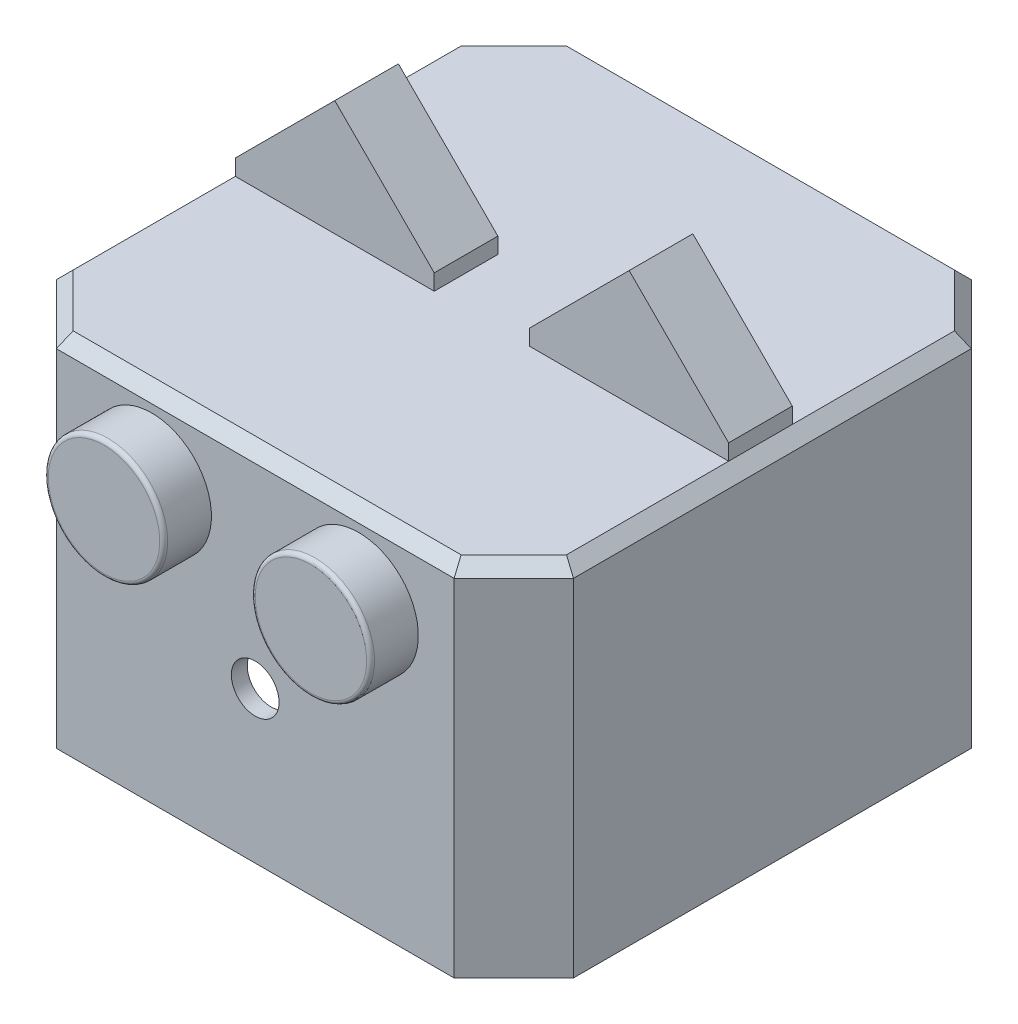
SolidWorks part; units mm, degrees
ref_plane "Alzado" through (0, 0, 0) normal (0, 0, 1) x (1, 0, 0)
ref_plane "Planta" through (0, 0, 0) normal (0, 1, 0) x (1, 0, 0)
ref_plane "Vista lateral" through (0, 0, 0) normal (1, 0, 0) x (0, 0, -1)
sketch "Croquis1" plane through (0, 0, 0) normal (0, 1, 0) x (1, 0, 0)
  line L1 (-25, -32.5) -> (25, -32.5)
  line L3 (-25, 32.5) -> (25, 32.5)
  line L5 (-25, -32.5) -> (25, 32.5) construction
  line L6 (-25, 32.5) -> (25, -32.5) construction
  line L10 (32.5, 25) -> (32.5, -25)
  line L11 (25, -32.5) -> (32.5, -25)
  line L12 (32.5, 25) -> (25, 32.5)
  line L13 (-32.5, 25) -> (-32.5, -25)
  line L14 (-32.5, -25) -> (-25, -32.5)
  line L15 (-32.5, 25) -> (-25, 32.5)
  point P0 (0, 0)
  point P10 (0, 32.5)
  dimension "D1" = 65
  dimension "D2" = 65
  dimension "D3" = 50
  dimension "D4" = 50
  dimension "D5" = 25
  dimension "D6" = 25
extrude "Saliente-Extruir1" add sketch "Croquis1" along normal blind 45
shell "Vaciado2" thickness 2 removed face at (0, 0, 0)
chamfer "Chaflán3" distance 1.5 angle 45 8 edges at (0, 45, -32.5) (32.5, 45, 0) (0, 45, 32.5) (-32.5, 45, 0) (-28.75, 45, 28.75) (28.75, 45, 28.75) (28.75, 45, -28.75) (-28.75, 45, -28.75)
sketch "Croquis2" plane through (0, 0, 32.5) normal (0, 0, 1) x (1, 0, 0)
  line L0 (0, 0) -> (0, 6.916) construction
  circle A0 centre (13, 35) radius 7.5
  circle A1 centre (-13, 35) radius 7.5
  dimension "D1" = 15
  dimension "D2" = 13
  dimension "D3" = 35
extrude "Saliente-Extruir2" add sketch "Croquis2" along normal blind 6
sketch "Croquis4" plane through (0, 0, 30.5) normal (0, 0, -1) x (-1, 0, 0)
  line L0 (0, 0) -> (0, 4.7403) construction
  line L1 (0, 0) -> (0, 6.916) construction
  circle A0 centre (-13, 35) radius 5
  circle A1 centre (13, 35) radius 5
  dimension "D1" = 10
extrude "Cortar-Extruir2" cut sketch "Croquis4" against normal blind 5
fillet "Redondeo1" radius 0.5 2 edges at (-20.5, 35, 38.5) (20.5, 35, 38.5)
sketch "Croquis5" plane through (0, 0, 32.5) normal (0, 0, 1) x (1, 0, 0)
  circle A0 centre (0, 19) radius 3
  dimension "D2" = 6
  dimension "D1" = 19
extrude "Cortar-Extruir3" cut sketch "Croquis5" against normal blind 10
sketch "Croquis6" plane through (0, 0, -32.5) normal (0, 0, -1) x (-1, 0, 0)
  line L1 (-21, 3) -> (-15, 3)
  line L2 (-21, 3) -> (-21, 9)
  line L3 (-21, 9) -> (-15, 9)
  line L4 (-15, 3) -> (-15, 9)
  line L5 (-21, 3) -> (-15, 9) construction
  line L6 (-21, 9) -> (-15, 3) construction
  point P0 (-18, 6)
  dimension "D1" = 18
  dimension "D2" = 6
  dimension "D3" = 6
  dimension "D4" = 3
extrude "Cortar-Extruir4" cut sketch "Croquis6" against normal blind 10
sketch "Croquis13" plane through (0, 0, 35.5) normal (0, 0, -1) x (-1, 0, 0)
  circle A0 centre (-13, 35) radius 2.6
  circle A1 centre (13, 35) radius 2.6
  circle A2 centre (13, 35) radius 5
  circle A3 centre (-13, 35) radius 5
  dimension "D1" = 5.2
  dimension "D2" = 5.2
extrude "Saliente-Extruir8" add sketch "Croquis13" along normal blind 5
sketch "Croquis7" plane through (0, 0, 30.5) normal (0, 0, -1) x (-1, 0, 0)
  line L0 (24.1716, 0) -> (-24.1716, 0) construction
  line L1 (-13.58, 8.5) -> (-9.58, 8.5)
  line L2 (-13.58, 8.5) -> (-13.58, 12.5)
  line L3 (-13.58, 12.5) -> (-9.58, 12.5)
  line L4 (-9.58, 8.5) -> (-9.58, 12.5)
  line L5 (-13.58, 8.5) -> (-9.58, 12.5) construction
  line L6 (-13.58, 12.5) -> (-9.58, 8.5) construction
  line L8 (-13.58, 26) -> (-9.58, 26)
  line L9 (-13.58, 26) -> (-13.58, 30)
  line L10 (-13.58, 30) -> (-9.58, 30)
  line L11 (-9.58, 26) -> (-9.58, 30)
  line L12 (-13.58, 26) -> (-9.58, 30) construction
  line L13 (-13.58, 30) -> (-9.58, 26) construction
  line L14 (13.43, 12.5) -> (9.43, 8.5) construction
  line L15 (13.43, 8.5) -> (9.43, 12.5) construction
  line L16 (9.43, 8.5) -> (9.43, 12.5)
  line L17 (13.43, 12.5) -> (9.43, 12.5)
  line L18 (13.43, 8.5) -> (13.43, 12.5)
  line L19 (13.43, 8.5) -> (9.43, 8.5)
  line L20 (13.43, 30) -> (9.43, 26) construction
  line L21 (13.43, 26) -> (9.43, 30) construction
  line L22 (9.43, 26) -> (9.43, 30)
  line L23 (13.43, 30) -> (9.43, 30)
  line L24 (13.43, 26) -> (13.43, 30)
  line L25 (13.43, 26) -> (9.43, 26)
  point P0 (-11.58, 10.5)
  point P8 (-11.58, 28)
  point P13 (0, 0)
  point P15 (11.43, 10.5)
  point P16 (11.43, 28)
  point P20 (11.43, 10.5)
  point P25 (11.43, 28)
  point P26 (-11.58, 28)
  point P27 (11.43, 28)
  point P28 (11.43, 10.5)
  point P29 (-11.58, 10.5)
  dimension "D1" = 10.5
  dimension "D2" = 4
  dimension "D3" = 4
  dimension "D4" = 11.58
  dimension "D5" = 4
  dimension "D6" = 4
  dimension "D7" = 28
  dimension "D8" = 23.01
  dimension "D9" = 23.01
  dimension "D10" = 4
  dimension "D11" = 4
  dimension "D12" = 4
  dimension "D13" = 4
  dimension "D14" = 10.5
  dimension "D15" = 28
extrude "Saliente-Extruir3" add sketch "Croquis7" along normal blind 1
sketch "Croquis8" plane through (0, 0, 29.5) normal (0, 0, -1) x (-1, 0, 0)
  line L0 (0, 0) -> (0, 4.8013) construction
  line L1 (24.1716, 0) -> (-24.1716, 0) construction
  circle A0 centre (-11.505, 10.4893) radius 2
  circle A1 centre (-11.505, 27.9763) radius 2
  circle A2 centre (11.505, 10.4893) radius 2
  circle A3 centre (11.505, 27.9763) radius 2
  dimension "D1" = 4
  dimension "D2" = 4
  dimension "D3" = 23.01
  dimension "D4" = 23.01
extrude "Saliente-Extruir4" add sketch "Croquis8" along normal blind 1
sketch "Croquis9" plane through (0, 0, 28.5) normal (0, 0, -1) x (-1, 0, 0)
  circle A0 centre (-11.505, 27.9763) radius 1.6
  circle A1 centre (-11.505, 10.4893) radius 1.6
  circle A2 centre (11.505, 10.4893) radius 1.6
  circle A3 centre (11.505, 27.9763) radius 1.6
  dimension "D1" = 3.2
  dimension "D2" = 3.2
  dimension "D3" = 3.2
  dimension "D4" = 3.2
extrude "Cortar-Extruir5" cut sketch "Croquis9" against normal blind 2
sketch "Croquis10" plane through (0, 45, 0) normal (0, 1, 0) x (1, 0, 0)
  line L0 (-31, 24.3787) -> (-31, -24.3787) construction
  line L1 (-31, -4) -> (-6, -4)
  line L2 (-31, -4) -> (-31, 4)
  line L3 (-31, 4) -> (-6, 4)
  line L4 (-6, -4) -> (-6, 4)
  line L5 (-31, -4) -> (-6, 4) construction
  line L6 (-31, 4) -> (-6, -4) construction
  line L7 (0, 0) -> (0, 7.307) construction
  line L8 (31, 4) -> (6, -4) construction
  line L9 (31, -4) -> (6, 4) construction
  line L10 (6, -4) -> (6, 4)
  line L11 (31, 4) -> (6, 4)
  line L12 (31, -4) -> (31, 4)
  line L13 (31, -4) -> (6, -4)
  point P0 (-18.5, 0)
  point P14 (18.5, 0)
  dimension "D1" = 25
  dimension "D2" = 8
extrude "Saliente-Extruir5" add sketch "Croquis10" along normal blind 2
sketch "Croquis11" plane through (0, 0, 4) normal (0, 0, 1) x (1, 0, 0)
  line L0 (-31, 47) -> (-6, 47)
  line L1 (-6, 47) -> (-18.5, 59.5)
  line L2 (-31, 47) -> (-18.5, 59.5)
  line L3 (0, 45) -> (0, 52) construction
  line L4 (-24.3787, 45) -> (24.3787, 45) construction
  line L5 (31, 47) -> (18.5, 59.5)
  line L6 (6, 47) -> (18.5, 59.5)
  line L7 (31, 47) -> (6, 47)
extrude "Saliente-Extruir6" add sketch "Croquis11" against normal blind 8
sketch "Croquis12" plane through (0, 43, 0) normal (0, -1, 0) x (1, 0, 0)
  line L0 (0, 0) -> (-5.199, 0) construction
  line L1 (-21.9, -8.93) -> (21.9, -8.93) construction
  line L2 (-21.9, -8.93) -> (-21.9, 8.93) construction
  line L3 (-21.9, 8.93) -> (21.9, 8.93) construction
  line L4 (21.9, -8.93) -> (21.9, 8.93) construction
  line L5 (-21.9, -8.93) -> (21.9, 8.93) construction
  line L6 (-21.9, 8.93) -> (21.9, -8.93) construction
  line L7 (0, 0) -> (0, 4.1573) construction
  circle A0 centre (-20.65, 7.68) radius 0.8
  circle A1 centre (-20.65, 7.68) radius 1.15
  circle A2 centre (-20.65, -7.68) radius 1.15
  circle A3 centre (-20.65, -7.68) radius 0.8
  circle A4 centre (20.65, 7.68) radius 1.15
  circle A5 centre (20.65, 7.68) radius 0.8
  circle A6 centre (20.65, -7.68) radius 1.15
  circle A7 centre (20.65, -7.68) radius 0.8
  point P0 (0, 0)
  dimension "D6" = 1.6
  dimension "D4" = 2.3
  dimension "D1" = 43.8
  dimension "D2" = 17.86
  dimension "D3" = 1.25
  dimension "D7" = 1.25
extrude "Saliente-Extruir7" add sketch "Croquis12" along normal blind 6
sketch "Croquis14" plane through (0, 43, 0) normal (0, -1, 0) x (1, 0, 0)
  line L1 (-22.15, 6.43) -> (-19.15, 6.43)
  line L2 (-22.15, 6.43) -> (-22.15, 8.93)
  line L3 (-22.15, 8.93) -> (-19.15, 8.93)
  line L4 (-19.15, 6.43) -> (-19.15, 8.93)
  line L5 (-22.15, 6.43) -> (-19.15, 8.93) construction
  line L6 (-22.15, 8.93) -> (-19.15, 6.43) construction
  line L7 (-22.15, -8.93) -> (-19.15, -8.93)
  line L8 (-22.15, -8.93) -> (-22.15, -6.43)
  line L9 (-22.15, -6.43) -> (-19.15, -6.43)
  line L10 (-19.15, -8.93) -> (-19.15, -6.43)
  line L11 (-22.15, -8.93) -> (-19.15, -6.43) construction
  line L12 (-22.15, -6.43) -> (-19.15, -8.93) construction
  line L13 (19.15, 6.43) -> (22.15, 6.43)
  line L14 (19.15, 6.43) -> (19.15, 8.93)
  line L15 (19.15, 8.93) -> (22.15, 8.93)
  line L16 (22.15, 6.43) -> (22.15, 8.93)
  line L17 (19.15, 6.43) -> (22.15, 8.93) construction
  line L18 (19.15, 8.93) -> (22.15, 6.43) construction
  line L19 (19.15, -8.93) -> (22.15, -8.93)
  line L20 (19.15, -8.93) -> (19.15, -6.43)
  line L21 (19.15, -6.43) -> (22.15, -6.43)
  line L22 (22.15, -8.93) -> (22.15, -6.43)
  line L23 (19.15, -8.93) -> (22.15, -6.43) construction
  line L24 (19.15, -6.43) -> (22.15, -8.93) construction
  point P0 (-20.65, 7.68)
  point P6 (-20.65, -7.68)
  point P12 (20.65, 7.68)
  point P18 (20.65, -7.68)
  dimension "D1" = 3
  dimension "D2" = 2.5
  dimension "D3" = 3
  dimension "D4" = 2.5
  dimension "D5" = 3
  dimension "D6" = 2.5
  dimension "D7" = 3
  dimension "D8" = 2.5
extrude "Saliente-Extruir9" add sketch "Croquis14" along normal blind 5
sketch "Croquis15" plane through (-32.5, 0, 0) normal (-1, 0, 0) x (0, 0, 1)
  line L1 (-6, 42.5) -> (6, 42.5)
  line L2 (-6, 42.5) -> (-6, 34.5)
  line L3 (-6, 34.5) -> (6, 34.5)
  line L4 (6, 42.5) -> (6, 34.5)
  dimension "D1" = 8
  dimension "D2" = 12
  dimension "D3" = 1
  dimension "D4" = 19
extrude "Cortar-Extruir6" cut sketch "Croquis15" against normal blind 2
